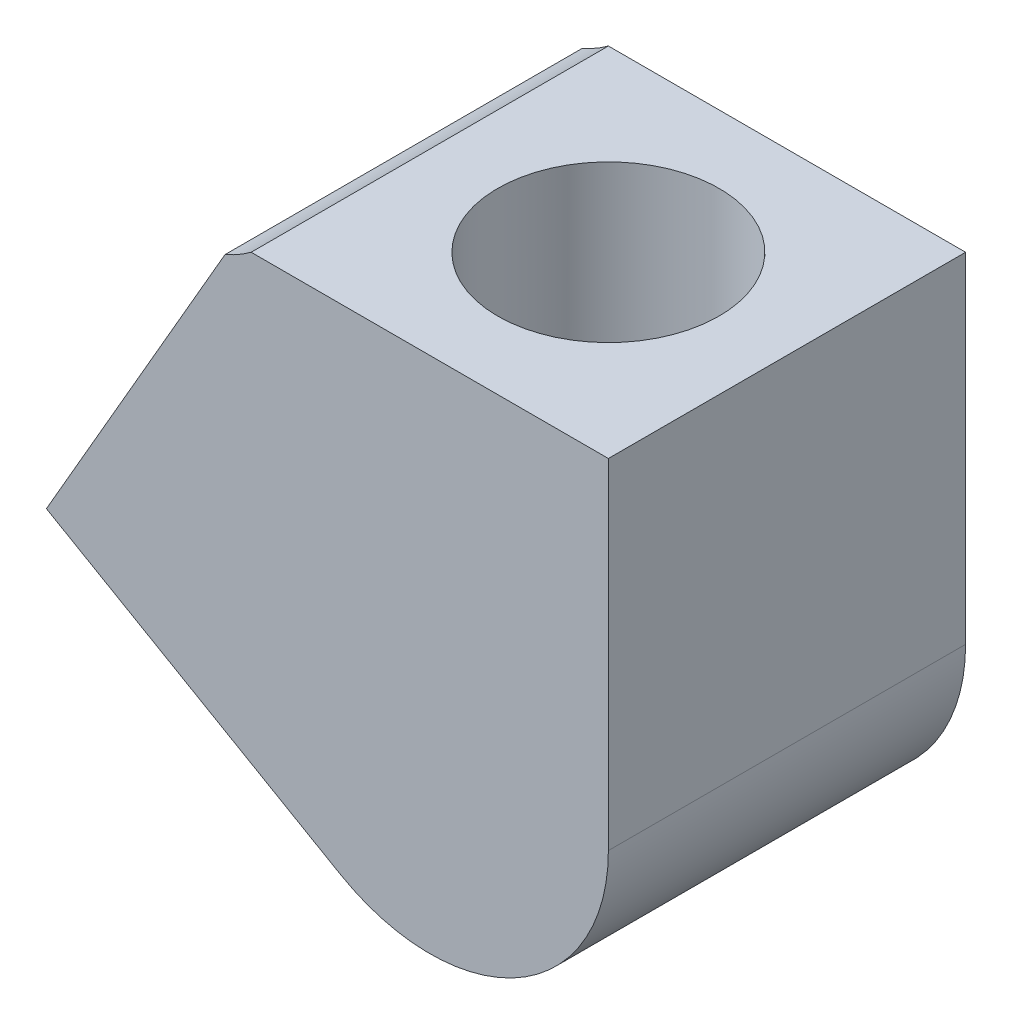
SolidWorks part; units mm, degrees
ref_plane "Front Plane" through (0, 0, 0) normal (0, 0, 1) x (1, 0, 0)
ref_plane "Top Plane" through (0, 0, 0) normal (0, 1, 0) x (1, 0, 0)
ref_plane "Right Plane" through (0, 0, 0) normal (1, 0, 0) x (0, 0, -1)
sketch "Sketch2" plane through (0, 0, 0) normal (0, 1, 0) x (1, 0, 0)
  line L1 (-13.15, -13.15) -> (13.15, -13.15)
  line L2 (-13.15, -13.15) -> (-13.15, 13.15)
  line L3 (-13.15, 13.15) -> (13.15, 13.15)
  line L4 (13.15, -13.15) -> (13.15, 13.15)
  circle A0 centre (0, 0) radius 8.15
  circle A1 centre (0, 0) radius 13.15
  dimension "D1" = 16.3
  dimension "D2" = 5
extrude "Boss-Extrude1" add sketch "Sketch2" along normal blind 25 contours A1 L3 L2 | A1 A0 | A1 L4 L3 | A1 L1 L4 | A1 L2 L1 region at (-10.2127, 0, 10.2127) region at (10.2127, 0, 10.2127) region at (-9.0355, 0, 9.0355) region at (-10.2127, 0, -10.2127) region at (10.2127, 0, -10.2127)
sketch "Sketch3" plane through (0, 0, 0) normal (0, 0, 1) x (1, 0, 0)
  line L0 (0, 0) -> (-25, 14.4338) construction
  line L2 (-6.575, -11.3882) -> (-28.2256, 1.1118)
  line L3 (-28.2256, 1.1118) -> (-15.0756, 23.8882)
  line L4 (-15.0756, 23.8882) -> (6.575, 11.3882)
  line L5 (-13.15, 25) -> (-13.15, 0) construction
  circle A0 centre (0, 0) radius 13.15
  point P9 (0, 0)
  dimension "D1" = 60
  dimension "D2" = 25
  dimension "D3" = 25
extrude "Boss-Extrude2" add sketch "Sketch3" along normal blind 13.15 and the other way blind 13.15 contours A0 | A0 L0 L3 L2 | L0 A0 L4 L3 region at (-18.6806, 2.3852, 0) region at (-11.4059, 14.9853, 0) region at (-3.3072, 12.3427, 0)
sketch "Sketch4" plane through (-21.6506, 12.5, 0) normal (-0.866, 0.5, 0) x (0, 0, 1)
  circle A0 centre (0, 0) radius 8.15
  dimension "D1" = 16.3
extrude "Cut-Extrude1" cut sketch "Sketch4" against normal blind 25
sketch "Sketch5" plane through (0, 25, 0) normal (0, 1, 0) x (1, 0, 0)
  circle A0 centre (0, 0) radius 8.15
  arc A1 (6.575, 4.8158) -> (6.575, -4.8158) centre (0, 0) ccw construction
extrude "Cut-Extrude2" cut sketch "Sketch5" against normal blind 25
fillet "Fillet1" radius 10 1 edges at (-13.15, 22.7765, 0)
